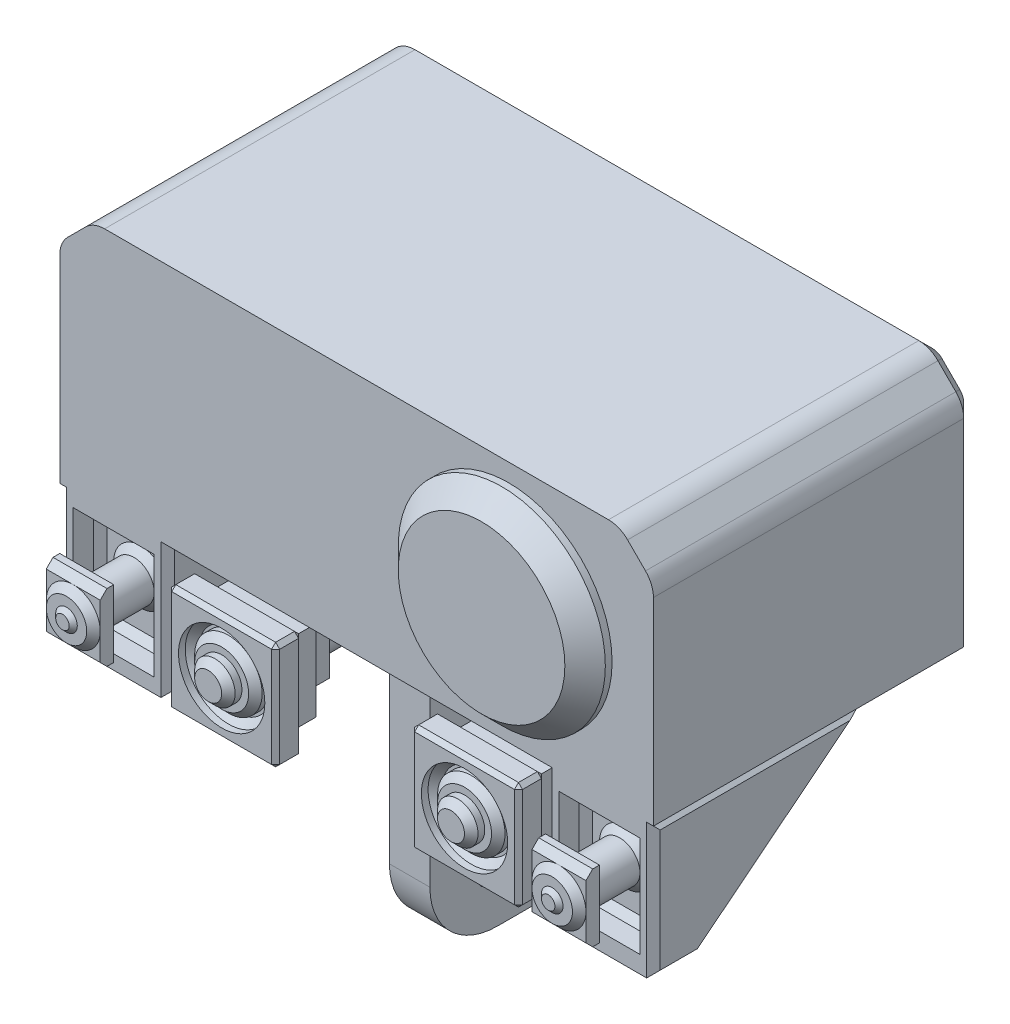
SolidWorks part; units mm, degrees
material "ABS"
ref_plane "Front Plane" through (0, 0, 0) normal (0, 0, 1) x (1, 0, 0)
ref_plane "Top Plane" through (0, 0, 0) normal (0, 1, 0) x (1, 0, 0)
ref_plane "Right Plane" through (0, 0, 0) normal (1, 0, 0) x (0, 0, -1)
sketch "Sketch1" plane through (0, 0, 0) normal (0, 1, 0) x (1, 0, 0)
  line L1 (-220, 120) -> (220, 120)
  line L2 (-220, 120) -> (-220, -120)
  line L3 (-220, -120) -> (220, -120)
  line L4 (220, 120) -> (220, -120)
  line L5 (-220, 120) -> (220, -120) construction
  line L6 (-220, -120) -> (220, 120) construction
  point P0 (0, 0)
  dimension "D1" = 440
  dimension "D2" = 240
extrude "Boss-Extrude1" add sketch "Sketch1" along normal blind 180
sketch "Sketch2" plane through (0, 0, 0) normal (0, -1, 0) x (1, 0, 0)
  line L1 (-220, 120) -> (-140, 120)
  line L2 (-220, 120) -> (-220, -40)
  line L3 (-220, -40) -> (-140, -40)
  line L4 (-140, 120) -> (-140, -40)
  line L5 (220, 120) -> (140, 120)
  line L6 (220, 120) -> (220, -40)
  line L7 (220, -40) -> (140, -40)
  line L8 (140, 120) -> (140, -40)
  dimension "D1" = 80
  dimension "D2" = 80
  dimension "D3" = 160
  dimension "D4" = 160
extrude "Boss-Extrude2" add sketch "Sketch2" along normal blind 100 separate body
sketch "Sketch5" plane through (0, 0, 0) normal (0, -1, 0) x (-1, 0, 0)
  line L0 (140, 40) -> (140, -120) construction
  line L1 (140, -102.0564) -> (-140, -102.0564)
  line L2 (140, -102.0564) -> (140, 21.8541)
  line L3 (140, 21.8541) -> (-140, 21.8541)
  line L4 (-140, -102.0564) -> (-140, 21.8541)
  line L5 (-140, -120) -> (-140, 40) construction
extrude "Boss-Extrude3" add sketch "Sketch5" along normal blind 10 separate body
sketch "Sketch6" plane through (-220, 0, 0) normal (-1, 0, 0) x (0, 0, 1)
  line L0 (-40, 0) -> (85.6822, -100)
  line L1 (120, -100) -> (-40, -100) construction
  line L2 (85.6822, -100) -> (-40, -100)
  line L3 (-40, -100) -> (-40, 0)
extrude "Cut-Extrude1" cut sketch "Sketch6" against normal up to vertex
sketch "Sketch7" plane through (0, 0, 120) normal (0, 0, 1) x (1, 0, 0)
  line L0 (-220, 180) -> (220, 180) construction
  circle A0 centre (112.6193, 90) radius 71.1159
  dimension "D1" = 90
extrude "Cut-Extrude2" cut sketch "Sketch7" against normal blind 20
chamfer "Chamfer1" distance 25 angle 45 2 edges at (220, 180, 0) (-220, 180, 0)
fillet "Fillet1" radius 20 4 edges at (220, 155, 0) (195, 180, 0) (-220, 155, 0) (-195, 180, 0)
sketch "Sketch8" plane through (0, 0, 120) normal (0, 0, 1) x (1, 0, 0)
  line L0 (-140, -100) -> (-140, 0) construction
  line L1 (-130, -15) -> (-50, -15)
  line L2 (-130, -15) -> (-130, -95)
  line L3 (-130, -95) -> (-50, -95)
  line L4 (-50, -15) -> (-50, -95)
  line L5 (50, -15) -> (130, -15)
  line L6 (50, -15) -> (50, -95)
  line L7 (50, -95) -> (130, -95)
  line L8 (130, -15) -> (130, -95)
  line L9 (140, -10) -> (-140, -10) construction
  line L10 (140, -100) -> (140, 0) construction
  point P10 (-140, -50)
  dimension "D1" = 80
  dimension "D2" = 80
  dimension "D3" = 80
  dimension "D4" = 80
  dimension "D5" = 10
  dimension "D6" = 5
  dimension "D7" = 5
  dimension "D8" = 10
extrude "Boss-Extrude4" add sketch "Sketch8" along normal mid plane 20 separate body
sketch "Sketch9" plane through (0, 0, 110) normal (0, 0, -1) x (-1, 0, 0)
  line L0 (50, -95) -> (50, -15) construction
  line L1 (-120, -25) -> (-60, -25)
  line L2 (-120, -25) -> (-120, -85)
  line L3 (-120, -85) -> (-60, -85)
  line L4 (-60, -25) -> (-60, -85)
  line L5 (-120, -25) -> (-60, -85) construction
  line L6 (-120, -85) -> (-60, -25) construction
  line L7 (60, -25) -> (120, -25)
  line L8 (60, -25) -> (60, -85)
  line L9 (60, -85) -> (120, -85)
  line L10 (120, -25) -> (120, -85)
  line L11 (60, -25) -> (120, -85) construction
  line L12 (60, -85) -> (120, -25) construction
  line L13 (-130, -95) -> (-130, -15) construction
  line L14 (130, -95) -> (50, -95) construction
  line L15 (-50, -95) -> (-130, -95) construction
  point P0 (-90, -55)
  point P5 (90, -55)
  dimension "D1" = 60
  dimension "D2" = 60
  dimension "D3" = 60
  dimension "D4" = 60
  dimension "D5" = 10
  dimension "D6" = 10
  dimension "D7" = 10
  dimension "D8" = 10
extrude "Boss-Extrude5" add sketch "Sketch9" along normal blind 20
sketch "Sketch10" plane through (0, 0, 90) normal (0, 0, -1) x (-1, 0, 0)
  line L0 (-120, -25) -> (-120, -85) construction
  line L1 (-110, -35) -> (-70, -35)
  line L2 (-110, -35) -> (-110, -75)
  line L3 (-110, -75) -> (-70, -75)
  line L4 (-70, -35) -> (-70, -75)
  line L5 (-110, -35) -> (-70, -75) construction
  line L6 (-110, -75) -> (-70, -35) construction
  line L7 (-120, -85) -> (-60, -85) construction
  line L9 (70, -35) -> (110, -35)
  line L10 (70, -35) -> (70, -75)
  line L11 (70, -75) -> (110, -75)
  line L12 (110, -35) -> (110, -75)
  line L13 (70, -35) -> (110, -75) construction
  line L14 (70, -75) -> (110, -35) construction
  line L15 (60, -25) -> (60, -85) construction
  point P0 (-90, -55)
  point P9 (90, -55)
  dimension "D1" = 10
  dimension "D2" = 40
  dimension "D3" = 10
  dimension "D4" = 40
  dimension "D5" = 10
  dimension "D6" = 40
extrude "Boss-Extrude6" add sketch "Sketch10" along normal blind 20
sketch "Sketch11" plane through (0, 0, 70) normal (0, 0, -1) x (-1, 0, 0)
  circle A0 centre (-90, -55) radius 17
  circle A1 centre (90, -55) radius 17
  dimension "D1" = 34
  dimension "D2" = 34
extrude "Boss-Extrude7" add sketch "Sketch11" along normal blind 100
sketch "Sketch12" plane through (0, 0, -30) normal (0, 0, -1) x (-1, 0, 0)
  circle A0 centre (-90, -55) radius 28.2843
  circle A1 centre (90, -55) radius 28.2843
extrude "Boss-Extrude8" add sketch "Sketch12" along normal blind 20
sketch "Sketch16" plane through (0, 0, -50) normal (0, 0, -1) x (-1, 0, 0)
  line L5 (-130, -15) -> (-50, -15)
  line L6 (-130, -15) -> (-130, -95)
  line L7 (-130, -95) -> (-50, -95)
  line L8 (-50, -15) -> (-50, -95)
  line L9 (50, -15) -> (130, -15)
  line L10 (50, -15) -> (50, -95)
  line L11 (50, -95) -> (130, -95)
  line L12 (130, -15) -> (130, -95)
extrude "Boss-Extrude10" add sketch "Sketch16" along normal blind 30
sketch "Sketch19" plane through (0, -10, 0) normal (0, -1, 0) x (-1, 0, 0)
  line L0 (-140, 40) -> (-140, -85.6822) construction
  line L1 (-107, -17.9514) -> (-73, -17.9514)
  line L2 (-107, -17.9514) -> (-107, -39.8231)
  line L3 (-107, -39.8231) -> (-73, -39.8231)
  line L4 (-73, -17.9514) -> (-73, -39.8231)
  line L5 (73, -17.9514) -> (107, -17.9514)
  line L6 (73, -17.9514) -> (73, -39.8231)
  line L7 (73, -39.8231) -> (107, -39.8231)
  line L8 (107, -17.9514) -> (107, -39.8231)
  line L9 (140, -102.0564) -> (140, 21.8541) construction
  dimension "D1" = 34
  dimension "D2" = 34
  dimension "D3" = 33
  dimension "D4" = 33
extrude "Boss-Extrude12" add sketch "Sketch19" along normal blind 50
sketch "Sketch20" plane through (0, 0, 100) normal (0, 0, 1) x (1, 0, 0)
  circle A0 centre (112.6193, 90) radius 58.291
extrude "Boss-Extrude13" add sketch "Sketch20" along normal blind 30
chamfer "Chamfer5" distance 15 angle 45 1 edges at (170.9103, 90, 130)
sketch "Sketch22" plane through (0, 0, 130) normal (0, 0, 1) x (1, 0, 0)
  circle A0 centre (112.6193, 90) radius 32.5768
extrude "Boss-Extrude15" add sketch "Sketch22" along normal blind 10
chamfer "Chamfer6" distance 15 angle 45 1 edges at (145.196, 90, 140)
chamfer "Chamfer7" distance 5 1 edges at (155.9103, 90, 130)
sketch "Sketch23" plane through (0, 0, 120) normal (0, 0, 1) x (1, 0, 0)
  circle A0 centre (112.6193, 90) radius 76.755
extrude "Boss-Extrude16" add sketch "Sketch23" along normal blind 20 separate body
chamfer "Chamfer8" distance 15 angle 45 1 edges at (189.3742, 90, 140)
sketch "Sketch24" plane through (0, 0, 130) normal (0, 0, 1) x (1, 0, 0)
  circle A0 centre (-90, -55) radius 32
  circle A1 centre (90, -55) radius 32
  dimension "D1" = 64
  dimension "D2" = 64
extrude "Cut-Extrude3" cut sketch "Sketch24" against normal blind 10
sketch "Sketch25" plane through (0, 0, 120) normal (0, 0, 1) x (1, 0, 0)
  circle A0 centre (-90, -55) radius 25
  circle A1 centre (90, -55) radius 25
  dimension "D1" = 50
  dimension "D2" = 50
extrude "Boss-Extrude17" add sketch "Sketch25" along normal blind 10
sketch "Sketch26" plane through (0, 0, 130) normal (0, 0, 1) x (1, 0, 0)
  circle A0 centre (-90, -55) radius 15
  circle A1 centre (90, -55) radius 15
  dimension "D1" = 30
  dimension "D2" = 30
extrude "Boss-Extrude18" add sketch "Sketch26" along normal blind 10
chamfer "Chamfer9" distance 5 angle 45 6 edges at (122, -55, 120) (-58, -55, 120) (-65, -55, 130) (115, -55, 130) (105, -55, 140) (-75, -55, 140)
sketch "Sketch32" plane through (0, 0, 120) normal (0, 0, 1) x (1, 0, 0)
  line L0 (-140, -100) -> (-140, 0) construction
  line L1 (-210, -10.5929) -> (-150, -10.5929)
  line L2 (-210, -10.5929) -> (-210, -89.4071)
  line L3 (-210, -89.4071) -> (-150, -89.4071)
  line L4 (-150, -10.5929) -> (-150, -89.4071)
  line L5 (-210, -10.5929) -> (-150, -89.4071) construction
  line L6 (-210, -89.4071) -> (-150, -10.5929) construction
  line L7 (150, -12.6554) -> (210, -12.6554)
  line L8 (150, -12.6554) -> (150, -87.3446)
  line L9 (150, -87.3446) -> (210, -87.3446)
  line L10 (210, -12.6554) -> (210, -87.3446)
  line L11 (150, -12.6554) -> (210, -87.3446) construction
  line L12 (150, -87.3446) -> (210, -12.6554) construction
  line L13 (140, -100) -> (140, 0) construction
  point P0 (-180, -50)
  point P5 (180, -50)
  dimension "D1" = 60
  dimension "D2" = 10
  dimension "D3" = 60
  dimension "D4" = 74.6892
  dimension "D5" = 10
extrude "Cut-Extrude4" cut sketch "Sketch32" against normal blind 20
sketch "Sketch33" plane through (0, 0, 100) normal (0, 0, 1) x (1, 0, 0)
  circle A0 centre (-180, -50) radius 15
  circle A1 centre (180, -50) radius 15
  dimension "D1" = 30
  dimension "D2" = 30
extrude "Boss-Extrude20" add sketch "Sketch33" along normal blind 40
sketch "Sketch34" plane through (0, 0, 140) normal (0, 0, 1) x (1, 0, 0)
  line L1 (-200, -25) -> (-160, -25)
  line L2 (-200, -25) -> (-200, -75)
  line L3 (-200, -75) -> (-160, -75)
  line L4 (-160, -25) -> (-160, -75)
  line L5 (-200, -25) -> (-160, -75) construction
  line L6 (-200, -75) -> (-160, -25) construction
  line L7 (160, -25) -> (200, -25)
  line L8 (160, -25) -> (160, -75)
  line L9 (160, -75) -> (200, -75)
  line L10 (200, -25) -> (200, -75)
  line L11 (160, -25) -> (200, -75) construction
  line L12 (160, -75) -> (200, -25) construction
  point P0 (-180, -50)
  point P6 (180, -50)
  dimension "D1" = 40
  dimension "D2" = 40
  dimension "D3" = 50
  dimension "D4" = 50
extrude "Boss-Extrude21" add sketch "Sketch34" along normal blind 10
sketch "Sketch35" plane through (0, 0, 150) normal (0, 0, 1) x (1, 0, 0)
  circle A0 centre (-180, -50) radius 15
  circle A1 centre (180, -50) radius 15
  dimension "D1" = 30
  dimension "D2" = 30
extrude "Boss-Extrude22" add sketch "Sketch35" along normal blind 5
chamfer "Chamfer14" distance 5 angle 45 3 edges at (195, -50, 150) (180, -75, 150) (180, -25, 150)
chamfer "Chamfer15" distance 5 angle 45 3 edges at (-180, -75, 150) (-180, -25, 150) (-165, -50, 150)
sketch "Sketch36" plane through (0, 0, 155) normal (0, 0, 1) x (1, 0, 0)
  circle A0 centre (-180, -50) radius 10
  circle A1 centre (180, -50) radius 10
  dimension "D1" = 20
  dimension "D2" = 20
extrude "Boss-Extrude23" add sketch "Sketch36" along normal blind 3
chamfer "Chamfer17" distance 5 angle 45 1 edges at (-170, -50, 158)
chamfer "Chamfer18" distance 5 angle 45 1 edges at (190, -50, 158)
chamfer "Chamfer20" distance 10 angle 45 10 edges at (194.3694, 178.4776, -120) (0, 180, -120) (-194.3694, 178.4776, -120) (-207.5, 167.5, -120) (-218.4776, 154.3694, -120) (-220, 73.3579, -120) (0, 0, -120) (220, 73.3579, -120) (218.4776, 154.3694, -120) (207.5, 167.5, -120)
chamfer "Chamfer21" distance 5 angle 45 12 edges at (-140, -50, 120) (-140, 0, 40) (-140, -50, 22.8411) (-140, -100, 102.8411) (-220, -50, 120) (-220, -100, 102.8411) (-220, -50, 22.8411) (-220, 0, 40) (-180, -89.4071, 100) (-210, -50, 100) (-180, -10.5929, 100) (-150, -50, 100)
chamfer "Chamfer22" distance 5 angle 45 12 edges at (140, -50, 120) (140, -100, 102.8411) (140, -50, 22.8411) (140, 0, 40) (220, -50, 120) (220, 0, 40) (220, -50, 22.8411) (220, -100, 102.8411) (180, -87.3446, 100) (150, -50, 100) (180, -12.6554, 100) (210, -50, 100)
chamfer "Chamfer23" distance 3 angle 45 8 edges at (-90, -15, -80) (-130, -55, -80) (-90, -95, -80) (-50, -55, -80) (-90, -95, -50) (-130, -55, -50) (-90, -15, -50) (-50, -55, -50)
chamfer "Chamfer24" distance 3 angle 45 8 edges at (90, -95, -50) (50, -55, -50) (90, -15, -50) (130, -55, -50) (90, -15, -80) (50, -55, -80) (90, -95, -80) (130, -55, -80)
sketch "Sketch37" plane through (0, -10, 0) normal (0, -1, 0) x (1, 0, 0)
  line L0 (-140, -21.8541) -> (140, -21.8541) construction
  line L1 (6.3952, 102.0564) -> (36.3952, 102.0564)
  line L3 (6.3952, -21.8541) -> (36.3952, -21.8541)
  line L4 (36.3952, 102.0564) -> (36.3952, -21.8541)
  line L7 (6.3952, 102.0564) -> (6.3952, -21.8541)
  point P0 (0, 40.1012)
  dimension "D1" = 30
extrude "Boss-Extrude25" add sketch "Sketch37" along normal blind 180
sketch "Sketch39" plane through (6.3952, 0, 0) normal (-1, 0, 0) x (0, 0, 1)
  circle A1 centre (40.1012, -134.0463) radius 42
  dimension "D1" = 84
extrude "Cut-Extrude5" cut sketch "Sketch39" against normal blind 20
combine bodies "Combine5" operation type add bodies to combine 126 125 140 141 144
fillet "Fillet2" radius 50 2 edges at (21.3952, -190, -21.8541) (21.3952, -190, 102.0564)
scale "Scale1" scale about centroid uniform scaling yes scale factor 0.3
sketch "Sketch40" plane through (9.2024, 0, 0) normal (-1, 0, 0) x (0, 0, 1)
  line L0 (10.6316, 7.4479) -> (18.0553, 7.4479) construction
  line L1 (18.0553, 7.4479) -> (12.0449, 13.4583) construction
  line L2 (18.0553, 7.4479) -> (24.0657, 13.4583) construction
  line L3 (18.0553, 7.4479) -> (24.0657, 1.4375) construction
  line L4 (18.0553, 7.4479) -> (12.0449, 1.4375) construction
  circle A0 centre (12.0449, 13.4583) radius 1.75
  circle A1 centre (18.0553, 7.4479) radius 12.6 construction
  circle A2 centre (18.0553, 7.4479) radius 12.6 construction
  circle A3 centre (24.0657, 13.4583) radius 1.75
  circle A4 centre (18.0553, 7.4479) radius 12.6 construction
  circle A5 centre (24.0657, 1.4375) radius 1.75
  circle A6 centre (18.0553, 7.4479) radius 12.6 construction
  circle A7 centre (12.0449, 1.4375) radius 1.75
  circle A8 centre (18.0553, 7.4479) radius 12.6 construction
  point P17 (18.0553, 7.4479)
  dimension "D2" = 3.5
  dimension "D1" = 45
  dimension "D3" = 8.5
  dimension "D4" = 4
extrude "Cut-Extrude6" cut sketch "Sketch40" against normal up to next
